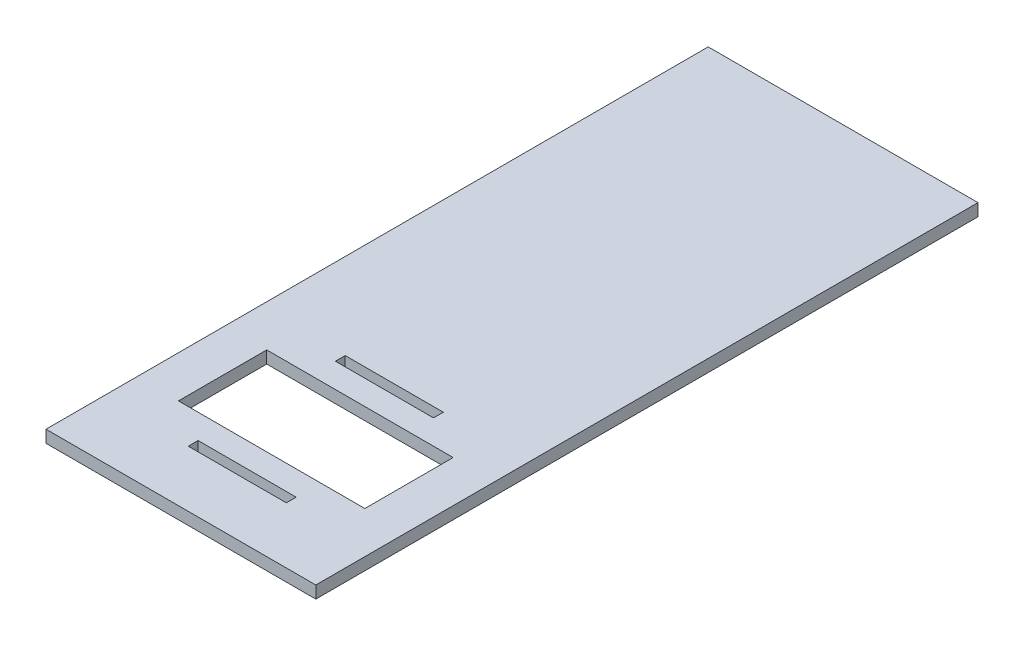
SolidWorks part; units mm, degrees
ref_plane "Front Plane" through (0, 0, 0) normal (0, 0, 1) x (1, 0, 0)
ref_plane "Top Plane" through (0, 0, 0) normal (0, 1, 0) x (1, 0, 0)
ref_plane "Right Plane" through (0, 0, 0) normal (1, 0, 0) x (0, 0, -1)
sketch "Sketch1" plane through (0, 0, 0) normal (0, 1, 0) x (1, 0, 0)
  line L1 (-69.85, -69.85) -> (69.85, -69.85)
  line L2 (-69.85, -69.85) -> (-69.85, 273.05)
  line L3 (-69.85, 273.05) -> (69.85, 273.05)
  line L4 (69.85, -69.85) -> (69.85, 273.05)
  line L5 (0, 273.05) -> (0, -69.85) construction
  line L6 (-69.85, 101.6) -> (69.85, 101.6) construction
  point P0 (0, 101.6)
  dimension "D1" = 342.9
  dimension "D2" = 139.7
  dimension "D3" = 101.6
extrude "Boss-Extrude1" add sketch "Sketch1" along normal blind 6.35
sketch "Sketch2" plane through (0, 6.35, 0) normal (0, 1, 0) x (1, 0, 0)
  line L1 (-48.26, -22.86) -> (48.26, -22.86)
  line L2 (-48.26, -22.86) -> (-48.26, 22.86)
  line L3 (-48.26, 22.86) -> (48.26, 22.86)
  line L4 (48.26, -22.86) -> (48.26, 22.86)
  line L5 (0, 22.86) -> (0, -22.86) construction
  line L6 (-48.26, 0) -> (48.26, 0) construction
  point P0 (0, 0)
  dimension "D1" = 45.72
  dimension "D2" = 96.52
extrude "Cut-Extrude1" cut sketch "Sketch2" against normal through all
sketch "Sketch3" plane through (0, 6.35, 0) normal (0, 1, 0) x (1, 0, 0)
  line L0 (48.26, 22.86) -> (-48.26, 22.86) construction
  line L1 (-25.4, 35.56) -> (25.4, 35.56)
  line L2 (-25.4, 35.56) -> (-25.4, 40.64)
  line L3 (-25.4, 40.64) -> (25.4, 40.64)
  line L4 (25.4, 35.56) -> (25.4, 40.64)
  point P4 (0, 35.56)
  dimension "D1" = 50.8
  dimension "D2" = 5.08
  dimension "D3" = 12.7
extrude "NeoPixel" cut sketch "Sketch3" against normal through all
sketch "Sketch4" plane through (0, 0, 0) normal (0, -1, 0) x (1, 0, 0)
  line L0 (25.4, -35.56) -> (25.4, -40.64) construction
  line L1 (-25.4, -40.64) -> (-25.4, -35.56) construction
  line L2 (-25.4, -35.56) -> (25.4, -35.56) construction
  circle A0 centre (13.208, -42.164) radius 1.016
  circle A1 centre (-13.208, -42.164) radius 1.016
  dimension "D4" = 2.032
  dimension "D1" = 12.192
  dimension "D2" = 12.192
  dimension "D3" = 6.604
extrude "Cut-Extrude3" cut sketch "Sketch4" against normal blind 5.08
mirror "Mirror2" about plane through (0, 0, 0) normal (0, 0, 1) of "Cut-Extrude3", "NeoPixel"
equation "\"D1@Sketch2\"=1.8in"
equation "\"D2@Sketch2\"=3.8in"
